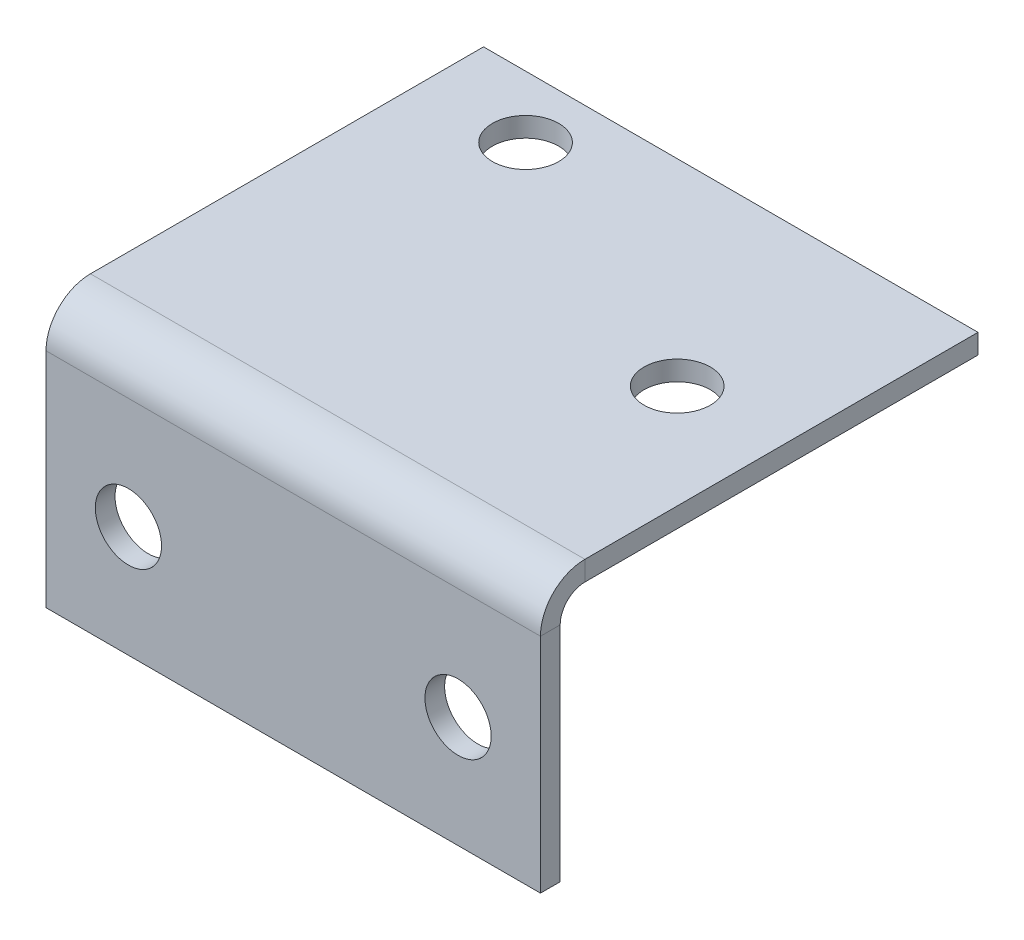
SolidWorks part; units mm, degrees
note: The reader was unsure of these and kept them because the rebuilt part matched: flange length of "Edge-Flange1".
ref_plane "Front Plane" through (0, 0, 0) normal (0, 0, 1) x (1, 0, 0)
ref_plane "Top Plane" through (0, 0, 0) normal (0, 1, 0) x (1, 0, 0)
ref_plane "Right Plane" through (0, 0, 0) normal (1, 0, 0) x (0, 0, -1)
sketch "Sketch7" plane through (0, 0, 0) normal (0, 0, 1) x (1, 0, 0)
  line L1 (-19.05, 9.525) -> (19.05, 9.525)
  line L2 (-19.05, 9.525) -> (-19.05, -9.525)
  line L3 (-19.05, -9.525) -> (19.05, -9.525)
  line L4 (19.05, 9.525) -> (19.05, -9.525)
  line L5 (-19.05, 9.525) -> (19.05, -9.525) construction
  line L6 (-19.05, -9.525) -> (19.05, 9.525) construction
  point P0 (0, 0)
  dimension "D1" = 19.05
  dimension "D2" = 38.1
base flange "Base-Flange1" sketch "Sketch7" thickness 1.5189 reverse thickness direction no parameters "D1"=1.905
edge flange "Edge-Flange1" sketch "Sketch14" flange angle 90 flange length 44.45 flange position material outside bend radius 1.905 thickness 1.5189 relief rectangular parameters "D6"=10
sketch "Sketch14" plane through (0, 9.525, -1.5189) normal (0, 1, 0) x (1, 0, 0)
  line L0 (19.05, 0) -> (-19.05, 0) construction
  line L1 (19.05, 0) -> (-19.05, 0)
  line L2 (-19.05, 0) -> (-19.05, 44.45)
  line L3 (-19.05, 44.45) -> (19.05, 44.45)
  line L4 (19.05, 44.45) -> (19.05, 0)
  dimension "D1" = 44.45
bend "EdgeBend1" bend radius 1.905 bend angle 90 parameters "D5"=1
hole_wizard " Clearance Hole2" [suppressed] positions "Sketch18" profile "Sketch17" hole size "#4" standard "ANSI Inch"
sketch "Sketch18" plane through (0, 11.0439, 0) normal (0, 1, 0) x (1, 0, 0)
  line L0 (-11.049, 29.6494) -> (11.049, 40.0634) construction
  line L2 (0, 34.8564) -> (0, 45.9689) construction
  line L3 (19.05, 45.9689) -> (-19.05, 45.9689) construction
  point P0 (11.049, 40.0634)
  point P2 (-11.049, 29.6494)
  dimension "D1" = 10.414
  dimension "D2" = 22.098
  dimension "D3" = 11.1125
sketch "Sketch17" plane through (11.049, 11.0439, -40.0634) normal (1, 0, 0) x (0, 0, 1)
  line L0 (0, 0) -> (0, 1.5189)
  line L1 (0, 1.5189) -> (2.5527, 1.5189)
  line L2 (2.5527, 1.5189) -> (2.5527, 0)
  line L5 (2.5527, 0) -> (0, 0)
  line L11 (0, -6.35) -> (0, 107.95) construction
  dimension "Thru Hole Dia." = 3.2639
  dimension "Thru Hole Depth" = 12.7
hole_wizard "#10 Clearance Hole1" positions "Sketch21" profile "Sketch20" hole size "#10" standard "ANSI Inch" end condition up to next
sketch "Sketch21" plane through (0, 0, 0) normal (0, 0, 1) x (1, 0, 0)
  line L0 (-19.05, -0.9525) -> (19.05, -0.9525) construction
  line L1 (-19.05, 7.62) -> (-19.05, -9.525) construction
  line L2 (19.05, -9.525) -> (19.05, 7.62) construction
  point P9 (-12.7, -0.9525)
  point P11 (12.7, -0.9525)
  dimension "D1" = 6.35
  dimension "D2" = 6.35
sketch "Sketch20" plane through (-12.7, -0.9525, 0) normal (1, 0, 0) x (0, -1, 0)
  line L0 (0, 0) -> (0, 1.5189)
  line L1 (0, 1.5189) -> (2.5527, 1.5189)
  line L2 (2.5527, 1.5189) -> (2.5527, 0)
  line L5 (2.5527, 0) -> (0, 0)
  line L11 (0, -6.35) -> (0, 107.95) construction
  dimension "Thru Hole Dia." = 5.1054
  dimension "Thru Hole Depth" = 1.5189
hole_wizard "#10 Clearance Hole2" positions "Sketch23" profile "Sketch22" hole size "#10" standard "ANSI Inch" end condition up to next
sketch "Sketch23" plane through (0, 9.525, 0) normal (0, -1, 0) x (-1, 0, 0)
  line L0 (-11.049, 18.5369) -> (11.049, 28.9509) construction
  line L2 (0, 23.7439) -> (0, 45.9689) construction
  line L3 (-19.05, 45.9689) -> (19.05, 45.9689) construction
  point P0 (-11.049, 18.5369)
  point P1 (11.049, 28.9509)
  dimension "D1" = 10.414
  dimension "D2" = 22.098
  dimension "D3" = 22.225
sketch "Sketch22" plane through (11.049, 9.525, -18.5369) normal (1, 0, 0) x (0, 0, -1)
  line L0 (0, 0) -> (0, 1.5189)
  line L1 (0, 1.5189) -> (2.5527, 1.5189)
  line L2 (2.5527, 1.5189) -> (2.5527, 0)
  line L5 (2.5527, 0) -> (0, 0)
  line L11 (0, -6.35) -> (0, 107.95) construction
  dimension "Thru Hole Dia." = 5.1054
  dimension "Thru Hole Depth" = 1.5189
sketch "Sketch24" plane through (0, 9.525, 0) normal (0, -1, 0) x (1, 0, 0)
  line L0 (19.05, -3.4239) -> (19.05, -45.9689) construction
  line L1 (-19.05, -45.9689) -> (19.05, -45.9689)
  line L2 (-19.05, -45.9689) -> (-19.05, -33.7134)
  line L3 (-19.05, -33.7134) -> (19.05, -33.7134)
  line L4 (19.05, -45.9689) -> (19.05, -33.7134)
  circle A0 centre (-11.049, -28.9509) radius 2.5527 construction
  dimension "D1" = 4.7625
extrude "Cut-Extrude1" cut sketch "Sketch24" against normal through all normal cut yes
sketch "Bend-Lines1" [suppressed] plane through (0, 0, 0) normal (0, 1, 0) x (1, 0, 0)
sketch "Bounding-Box1" [suppressed] plane through (0, 0, 0) normal (0, 1, 0) x (1, 0, 0)
sheet metal parameters "Sheet-Metal(4)" thickness 1.5189 parameters "D1"=1.905
flat pattern "Flat-Pattern(4)" [suppressed]
sketch "Bend-Lines2" plane through (0, 0, 0) normal (0, 1, 0) x (1, 0, 0)
sketch "Bounding-Box2" [suppressed] plane through (0, 0, 0) normal (0, 1, 0) x (1, 0, 0)
sheet metal parameters "Sheet-Metal(5)" thickness 1.5189 parameters "D1"=1.905
flat pattern "Flat-Pattern(4)" [suppressed]
sketch "Bend-Lines2" plane through (0, 0, 0) normal (0, 1, 0) x (1, 0, 0)
sketch "Bounding-Box2" [suppressed] plane through (0, 0, 0) normal (0, 1, 0) x (1, 0, 0)
bend of the flat pattern "Flatten-<EdgeBend1>1"
sheet metal parameters "Sheet-Metal(6)" thickness 1.5189 parameters "D1"=1.905
flat pattern "Flat-Pattern(4)" [suppressed]
sketch "Bend-Lines2" plane through (0, 0, 0) normal (0, 1, 0) x (1, 0, 0)
sketch "Bounding-Box2" [suppressed] plane through (0, 0, 0) normal (0, 1, 0) x (1, 0, 0)
bend of the flat pattern "Flatten-<EdgeBend1>1"
sheet metal parameters "Sheet-Metal(7)" thickness 1.5189 parameters "D1"=1.905
flat pattern "Flat-Pattern(4)"
sketch "Bend-Lines2" plane through (0, 0, 0) normal (0, 0, 1) x (1, 0, 0)
  line L0 (19.05, 9.7127) -> (-19.05, 9.7127) construction
  line L1 (19.05, 9.7127) -> (-19.05, 9.7127) construction
sketch3d "Bounding-Box2" [suppressed]
  line L0 (19.05, 48.0003, 0) -> (19.05, -9.525, 0) construction
  line L1 (-19.05, 48.0003, 0) -> (-19.05, -9.525, 0) construction
  line L2 (19.05, 48.0003, 0) -> (-19.05, 48.0003, 0) construction
  line L3 (19.05, -9.525, 0) -> (-19.05, -9.525, 0) construction
bend of the flat pattern "Flatten-<EdgeBend1>1"
sheet metal parameters "Sheet-Metal(8)" thickness 1.5189 parameters "D1"=1.905
flat pattern "Flat-Pattern(4)" [suppressed]
sketch "Bend-Lines2" plane through (0, 0, 0) normal (0, 1, 0) x (1, 0, 0)
sketch "Bounding-Box2" [suppressed] plane through (0, 0, 0) normal (0, 1, 0) x (1, 0, 0)
bend of the flat pattern "Flatten-<EdgeBend1>1"
sheet metal parameters "Sheet-Metal(9)" thickness 1.5189 parameters "D1"=1.905
flat pattern "Flat-Pattern(4)"
sketch "Bend-Lines2" plane through (0, 0, 0) normal (0, 0, 1) x (1, 0, 0)
  line L0 (19.05, 9.7127) -> (-19.05, 9.7127) construction
  line L1 (19.05, 9.7127) -> (-19.05, 9.7127) construction
sketch3d "Bounding-Box2" [suppressed]
  line L0 (19.05, 42.0948, 0) -> (19.05, -9.525, 0) construction
  line L1 (-19.05, 42.0948, 0) -> (-19.05, -9.525, 0) construction
  line L2 (19.05, 42.0948, 0) -> (-19.05, 42.0948, 0) construction
  line L3 (19.05, -9.525, 0) -> (-19.05, -9.525, 0) construction
bend of the flat pattern "Flatten-<EdgeBend1>1"
